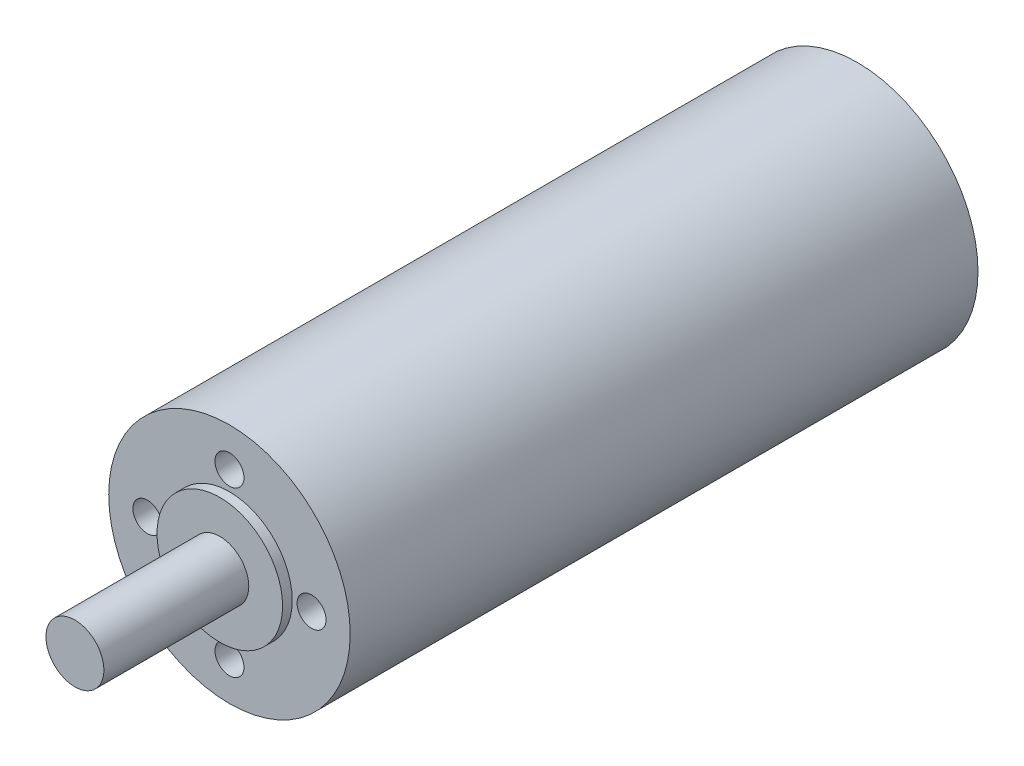
SolidWorks part; units mm, degrees
ref_plane "Plano frontal" through (0, 0, 0) normal (0, 0, 1) x (1, 0, 0)
ref_plane "Plano superior" through (0, 0, 0) normal (0, 1, 0) x (1, 0, 0)
ref_plane "Plano direito" through (0, 0, 0) normal (1, 0, 0) x (0, 0, -1)
sketch "Esboço1" plane through (0, 0, 0) normal (0, 0, 1) x (1, 0, 0)
  circle A0 centre (0, 0) radius 12.5
  dimension "D1" = 25
extrude "Ressalto-extrusão1" add sketch "Esboço1" along normal blind 65
sketch "Esboço2" plane through (0, 0, 65) normal (0, 0, 1) x (1, 0, 0)
  circle A0 centre (0, 0) radius 6.5
  dimension "D1" = 13
extrude "Ressalto-extrusão2" add sketch "Esboço2" along normal blind 1
sketch "Esboço3" plane through (0, 0, 66) normal (0, 0, 1) x (1, 0, 0)
  circle A0 centre (0, 0) radius 3
  dimension "D1" = 6
extrude "Ressalto-extrusão3" add sketch "Esboço3" along normal blind 15
sketch "Esboço4" plane through (0, 0, 65) normal (0, 0, 1) x (1, 0, 0)
  line L0 (0, -8.5) -> (0, 0) construction
  circle A0 centre (0, -8.5) radius 1.5
  dimension "D1" = 3
  dimension "D2" = 8.5
extrude "Corte-extrusão1" cut sketch "Esboço4" against normal blind 4
pattern_circular "PadrãoCircular1" count 4 over 360 about axis through (0, 0, 81) along (0, 0, -1) of "Corte-extrusão1"
